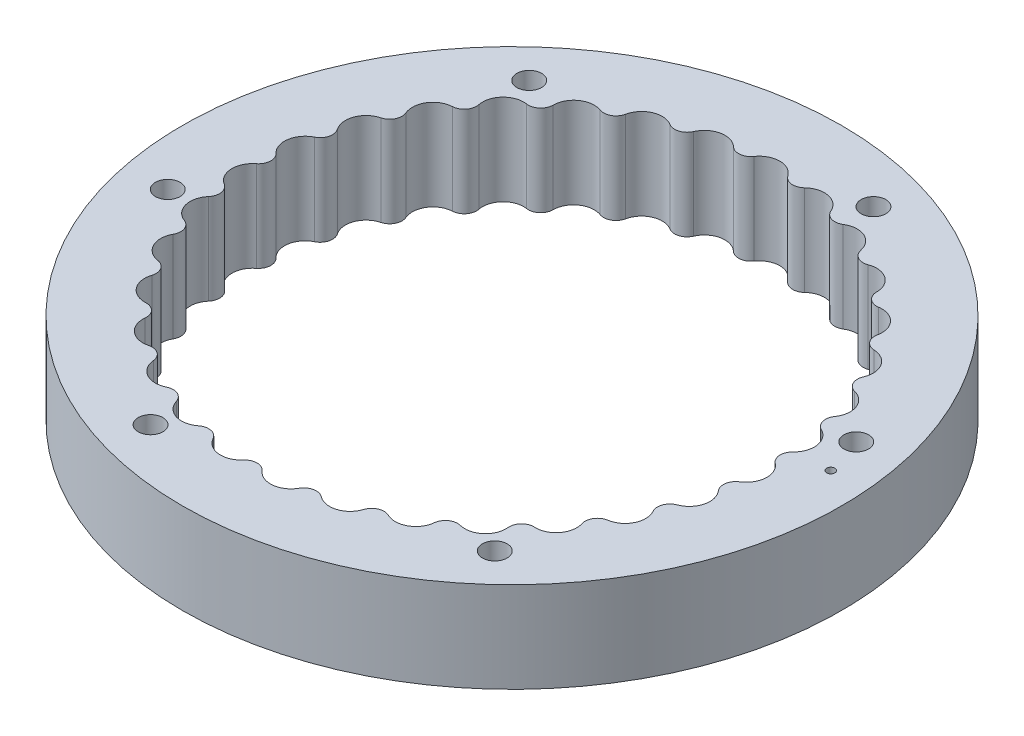
SolidWorks part; units mm, degrees
ref_plane "Front Plane" through (0, 0, 0) normal (0, 0, 1) x (1, 0, 0)
ref_plane "Top Plane" through (0, 0, 0) normal (0, 1, 0) x (1, 0, 0)
ref_plane "Right Plane" through (0, 0, 0) normal (1, 0, 0) x (0, 0, -1)
sketch "Sketch1" plane through (0, 0, 0) normal (0, 1, 0) x (1, 0, 0)
  arc A0 (-38.2573, 46.221) -> (-39.8947, 44.8153) centre (0, 0) ccw
  arc A1 (4.9957, 59.7917) -> (-4.9957, 59.7917) centre (0, 60) ccw
  arc A2 (16.9294, 57.5621) -> (7.1426, 59.5733) centre (12.0779, 58.7718) ccw
  arc A3 (28.17, 52.976) -> (18.9884, 56.9161) centre (23.6614, 55.1375) ccw
  arc A4 (38.2573, 46.221) -> (30.0568, 51.9287) centre (34.2761, 49.2458) ccw
  arc A5 (46.7784, 37.5737) -> (39.8947, 44.8153) centre (43.4876, 41.338) ccw
  arc A6 (53.3844, 27.3881) -> (48.0993, 35.8672) centre (50.9187, 31.7378) ccw
  arc A7 (57.8048, 16.0813) -> (54.3347, 25.4506) centre (56.2651, 20.8383) ccw
  arc A8 (59.8586, 4.1161) -> (58.3457, 13.9922) centre (59.3081, 9.0857) ccw
  arc A9 (59.4619, -8.0176) -> (59.968, 1.9608) centre (59.923, -3.039) ccw
  arc A10 (56.6308, -19.8231) -> (59.1351, -10.1508) centre (58.0846, -15.0392) ccw
  arc A11 (51.4812, -30.817) -> (55.8813, -21.8468) centre (53.8683, -26.4236) ccw
  arc A12 (44.2239, -40.5493) -> (50.3397, -32.6484) centre (47.4465, -36.7264) ccw
  arc A13 (35.1562, -48.6214) -> (42.7371, -42.1134) centre (39.0823, -45.5255) ccw
  arc A14 (24.6491, -54.703) -> (33.3849, -49.8542) centre (29.1181, -52.4608) ccw
  arc A15 (13.1329, -58.5451) -> (22.666, -55.5541) centre (17.9618, -57.2484) ccw
  arc A16 (1.079, -59.9903) -> (11.019, -58.9795) centre (6.0701, -59.6922) ccw
  arc A17 (-11.019, -58.9795) -> (-1.079, -59.9903) centre (-6.0701, -59.6922) ccw
  arc A18 (-22.666, -55.5541) -> (-13.1329, -58.5451) centre (-17.9618, -57.2484) ccw
  arc A19 (-33.3849, -49.8542) -> (-24.6491, -54.703) centre (-29.1181, -52.4608) ccw
  arc A20 (-42.7371, -42.1134) -> (-35.1562, -48.6214) centre (-39.0823, -45.5255) ccw
  arc A21 (-50.3397, -32.6484) -> (-44.2239, -40.5493) centre (-47.4465, -36.7264) ccw
  arc A22 (-55.8813, -21.8468) -> (-51.4812, -30.817) centre (-53.8683, -26.4236) ccw
  arc A23 (-59.1351, -10.1508) -> (-56.6308, -19.8231) centre (-58.0846, -15.0392) ccw
  arc A24 (-59.968, 1.9608) -> (-59.4619, -8.0176) centre (-59.923, -3.039) ccw
  arc A25 (-58.3457, 13.9922) -> (-59.8586, 4.1161) centre (-59.3081, 9.0857) ccw
  arc A26 (-54.3347, 25.4506) -> (-57.8048, 16.0813) centre (-56.2651, 20.8383) ccw
  arc A27 (-48.0993, 35.8672) -> (-53.3844, 27.3881) centre (-50.9187, 31.7378) ccw
  arc A28 (-39.8947, 44.8153) -> (-46.7784, 37.5737) centre (-43.4876, 41.338) ccw
  arc A29 (-30.0568, 51.9287) -> (-38.2573, 46.221) centre (-34.2761, 49.2458) ccw
  arc A30 (-18.9884, 56.9161) -> (-28.17, 52.976) centre (-23.6614, 55.1375) ccw
  arc A31 (-7.1426, 59.5733) -> (-16.9294, 57.5621) centre (-12.0779, 58.7718) ccw
  circle A32 centre (0, 0) radius 80
  arc A33 (-46.7784, 37.5737) -> (-48.0993, 35.8672) centre (0, 0) ccw
  arc A34 (-53.3844, 27.3881) -> (-54.3347, 25.4506) centre (0, 0) ccw
  arc A35 (-57.8048, 16.0813) -> (-58.3457, 13.9922) centre (0, 0) ccw
  arc A36 (-59.8586, 4.1161) -> (-59.968, 1.9608) centre (0, 0) ccw
  arc A37 (-59.4619, -8.0176) -> (-59.1351, -10.1508) centre (0, 0) ccw
  arc A38 (-56.6308, -19.8231) -> (-55.8813, -21.8468) centre (0, 0) ccw
  arc A39 (-51.4812, -30.817) -> (-50.3397, -32.6484) centre (0, 0) ccw
  arc A40 (-44.2239, -40.5493) -> (-42.7371, -42.1134) centre (0, 0) ccw
  arc A41 (-35.1562, -48.6214) -> (-33.3849, -49.8542) centre (0, 0) ccw
  arc A42 (-24.6491, -54.703) -> (-22.666, -55.5541) centre (0, 0) ccw
  arc A43 (-13.1329, -58.5451) -> (-11.019, -58.9795) centre (0, 0) ccw
  arc A44 (11.019, -58.9795) -> (13.1329, -58.5451) centre (0, 0) ccw
  arc A45 (-1.079, -59.9903) -> (1.079, -59.9903) centre (0, 0) ccw
  arc A46 (22.666, -55.5541) -> (24.6491, -54.703) centre (0, 0) ccw
  arc A47 (33.3849, -49.8542) -> (35.1562, -48.6214) centre (0, 0) ccw
  arc A48 (42.7371, -42.1134) -> (44.2239, -40.5493) centre (0, 0) ccw
  arc A49 (50.3397, -32.6484) -> (51.4812, -30.817) centre (0, 0) ccw
  arc A50 (55.8813, -21.8468) -> (56.6308, -19.8231) centre (0, 0) ccw
  arc A51 (59.1351, -10.1508) -> (59.4619, -8.0176) centre (0, 0) ccw
  arc A52 (59.968, 1.9608) -> (59.8586, 4.1161) centre (0, 0) ccw
  arc A53 (58.3457, 13.9922) -> (57.8048, 16.0813) centre (0, 0) ccw
  arc A54 (54.3347, 25.4506) -> (53.3844, 27.3881) centre (0, 0) ccw
  arc A55 (48.0993, 35.8672) -> (46.7784, 37.5737) centre (0, 0) ccw
  arc A56 (39.8947, 44.8153) -> (38.2573, 46.221) centre (0, 0) ccw
  arc A57 (30.0568, 51.9287) -> (28.17, 52.976) centre (0, 0) ccw
  arc A58 (18.9884, 56.9161) -> (16.9294, 57.5621) centre (0, 0) ccw
  arc A59 (7.1426, 59.5733) -> (4.9957, 59.7917) centre (0, 0) ccw
  arc A60 (-4.9957, 59.7917) -> (-7.1426, 59.5733) centre (0, 0) ccw
  arc A61 (-16.9294, 57.5621) -> (-18.9884, 56.9161) centre (0, 0) ccw
  arc A62 (-28.17, 52.976) -> (-30.0568, 51.9287) centre (0, 0) ccw
  dimension "D1" = 120
  dimension "D2" = 10
  dimension "D4" = 160
  dimension "D3" = 31
extrude "Boss-Extrude1" add sketch "Sketch1" along normal blind 22
fillet "Fillet1" radius 2.5 62 edges at (44.2239, 11, 40.5493) (42.7371, 11, 42.1134) (35.1562, 11, 48.6214) (33.3849, 11, 49.8542) (24.6491, 11, 54.703) (22.666, 11, 55.5541) (13.1329, 11, 58.5451) (11.019, 11, 58.9795) (1.079, 11, 59.9903) (-1.079, 11, 59.9903) (-11.019, 11, 58.9795) (-13.1329, 11, 58.5451) (-22.666, 11, 55.5541) (-24.6491, 11, 54.703) (-33.3849, 11, 49.8542) (-35.1562, 11, 48.6214) (-42.7371, 11, 42.1134) (-44.2239, 11, 40.5493) (-50.3397, 11, 32.6484) (-51.4812, 11, 30.817) (-55.8813, 11, 21.8468) (-56.6308, 11, 19.8231) (-59.1351, 11, 10.1508) (-59.4619, 11, 8.0176) (-59.968, 11, -1.9608) (-59.8586, 11, -4.1161) (-58.3457, 11, -13.9922) (-57.8048, 11, -16.0813) (-54.3347, 11, -25.4506) (-53.3844, 11, -27.3881) (50.3397, 11, 32.6484) (51.4812, 11, 30.817) (55.8813, 11, 21.8468) (56.6308, 11, 19.8231) (59.1351, 11, 10.1508) (59.4619, 11, 8.0176) (59.968, 11, -1.9608) (59.8586, 11, -4.1161) (58.3457, 11, -13.9922) (57.8048, 11, -16.0813) (54.3347, 11, -25.4506) (53.3844, 11, -27.3881) (48.0993, 11, -35.8672) (46.7784, 11, -37.5737) (38.2573, 11, -46.221) (39.8947, 11, -44.8153) (30.0568, 11, -51.9287) (28.17, 11, -52.976) (18.9884, 11, -56.9161) (16.9294, 11, -57.5621) (7.1426, 11, -59.5733) (4.9957, 11, -59.7917) (-4.9957, 11, -59.7917) (-7.1426, 11, -59.5733) (-16.9294, 11, -57.5621) (-18.9884, 11, -56.9161) (-28.17, 11, -52.976) (-30.0568, 11, -51.9287) (-38.2573, 11, -46.221) (-39.8947, 11, -44.8153) (-46.7784, 11, -37.5737) (-48.0993, 11, -35.8672)
fillet "Fillet2" radius 3 31 edges at (60.0791, 11, -3.0469) (59.4626, 11, 9.1093) (56.4117, 11, 20.8926) (51.0513, 11, 31.8205) (43.6009, 11, 41.4457) (34.3654, 11, 49.3741) (23.723, 11, 55.2812) (12.1094, 11, 58.9249) (0, 11, 60.1564) (-12.1094, 11, 58.9249) (-23.723, 11, 55.2812) (-34.3654, 11, 49.3741) (-43.6009, 11, 41.4457) (-51.0513, 11, 31.8205) (-56.4117, 11, 20.8926) (-59.4626, 11, 9.1093) (-60.0791, 11, -3.0469) (-58.236, 11, -15.0783) (-54.0086, 11, -26.4925) (58.236, 11, -15.0783) (54.0086, 11, -26.4925) (47.5702, 11, -36.8221) (39.1842, 11, -45.6441) (29.194, 11, -52.5975) (18.0086, 11, -57.3975) (6.0859, 11, -59.8477) (-6.0859, 11, -59.8477) (-18.0086, 11, -57.3975) (-29.194, 11, -52.5975) (-39.1842, 11, -45.6441) (-47.5702, 11, -36.8221)
sketch "Sketch3" plane through (0, 22, 0) normal (0, 1, 0) x (1, 0, 0)
  circle A0 centre (0, 0) radius 70 construction
  circle A1 centre (68.3193, 15.2469) radius 3
  circle A2 centre (47.3639, -51.5428) radius 3
  circle A3 centre (-20.9554, -66.7897) radius 3
  circle A4 centre (-68.3193, -15.2469) radius 3
  circle A5 centre (-47.3639, 51.5428) radius 3
  circle A6 centre (20.9554, 66.7897) radius 3
  point P17 (0, 0)
  dimension "D1" = 140
  dimension "D2" = 6
  dimension "D4" = 15.2469
  dimension "D3" = 6
extrude "Cut-Extrude1" cut sketch "Sketch3" against normal through all
sketch "Sketch4" plane through (0, 0, 0) normal (0, -1, 0) x (1, 0, 0)
  circle A0 centre (66.1432, 27.1816) radius 1
  dimension "D1" = 2
sketch "Sketch5" plane through (0, 22, 0) normal (0, 1, 0) x (1, 0, 0)
  circle A0 centre (71.247, 6.1342) radius 1
  dimension "D1" = 2
extrude "Cut-Extrude3" cut sketch "Sketch5" against normal blind 2
equation "\"R_ROLL\"= 5mm"
equation "\"D_SUN\"= 120mm"
equation "\"NUM_ROLL\"= 31"
equation "\"RHO\"= 1mm"
equation "\"D_SHAFT\"= 20mm"
equation "\"D_OUTPUT\"= 80mm"
equation "\"NUM_OUT\"= 8"
equation "\"R_OUT_ROLL\"= 5mm"
equation "\"D1@Sketch1\"=\"D_SUN\""
equation "\"D2@Sketch1\"=\"R_ROLL\"*2"
equation "\"D3@Sketch1\"=\"NUM_ROLL\""
equation "\"a\"= \"D_SUN\" + 30"
equation "\"D4@Sketch1\"=\"D_SUN\"+40"
